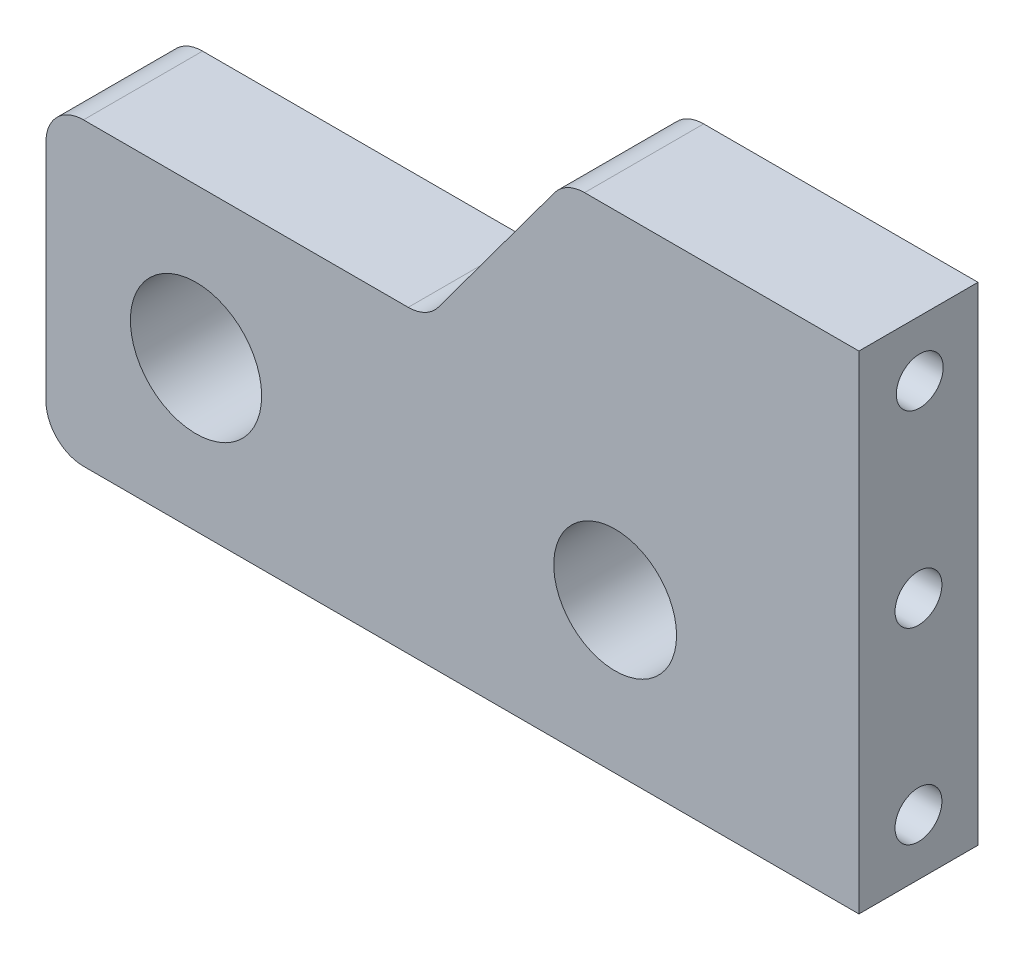
SolidWorks part; units mm, degrees
ref_plane "Front Plane" through (0, 0, 0) normal (0, 0, 1) x (1, 0, 0)
ref_plane "Top Plane" through (0, 0, 0) normal (0, 1, 0) x (1, 0, 0)
ref_plane "Right Plane" through (0, 0, 0) normal (1, 0, 0) x (0, 0, -1)
sketch "Sketch1" plane through (0, 0, 0) normal (0, 0, 1) x (1, 0, 0)
  line L0 (43.352, 8) -> (0, 8) construction
  line L1 (0, 0) -> (43.352, 0)
  line L2 (0, 0) -> (0, 16)
  line L3 (0, 16) -> (43.352, 16)
  line L4 (43.352, 0) -> (43.352, 16)
  circle A0 centre (8, 8) radius 3.5
  circle A1 centre (30.352, 8) radius 3.275
  dimension "D5" = 7
  dimension "D6" = 6.55
  dimension "D1" = 13
  dimension "D2" = 16
  dimension "D3" = 22.352
  dimension "D4" = 8
extrude "Boss-Extrude1" add sketch "Sketch1" along normal blind 6.35 contours L3 L4 L1 L2
extrude "Cut-Extrude1" cut sketch "Sketch1<6>" along normal blind 6.35 contours A0 L0 | L0 A0 | A1 region at (8, 6.5146, 0) region at (8, 9.4854, 0)
sketch "Sketch1<6>" plane through (0, 0, 0) normal (0, 0, 1) x (1, 0, 0) same geometry as "Sketch1"
fillet "Fillet1" radius 2 2 edges at (0, 16, 3.175) (0, 0, 3.175)
sketch "Sketch2" plane through (43.352, 0, 0) normal (1, 0, 0) x (0, 0, -1)
  line L0 (-6.35, 16) -> (0, 16) construction
  line L1 (-6.35, 0) -> (0, 0) construction
  line L4 (-6.35, 0) -> (-6.35, 16) construction
  circle A0 centre (-3.175, 13) radius 1.25
  circle A1 centre (-3.175, 3) radius 1.25
  dimension "D1" = 2.5
  dimension "D2" = 2.5
  dimension "D3" = 3
  dimension "D4" = 3
  dimension "D5" = 3.175
  dimension "D6" = 3.175
extrude "Cut-Extrude2" cut sketch "Sketch2" against normal blind 5
sketch "Sketch3" plane through (0, 0, 6.35) normal (0, 0, 1) x (1, 0, 0)
  line L0 (27.712, 26) -> (20.3263, 16)
  line L1 (43.352, 16) -> (27.712, 16)
  line L2 (43.352, 16) -> (43.352, 26)
  line L3 (43.352, 26) -> (27.712, 26)
  line L4 (27.712, 16) -> (27.712, 26)
  line L5 (2, 16) -> (43.352, 16) construction
  line M4 (43.352, 16) -> (2, 16)
  dimension "D1" = 10
extrude "Boss-Extrude2" add sketch "Sketch3" against normal blind 6.35 contours L4 L0 M4 | L4 L1 L2 L3 region at (25.2501, 19.3333, 6.35)
fillet "Fillet2" radius 2 2 edges at (20.3263, 16, 3.175) (27.712, 26, 3.175)
sketch "Sketch4" plane through (43.352, 0, 0) normal (1, 0, 0) x (0, 0, -1)
  line L0 (0, 26) -> (-6.35, 26) construction
  circle A0 centre (-3.1057, 23) radius 1.25
  dimension "D2" = 2.5
  dimension "D1" = 3
extrude "Cut-Extrude3" cut sketch "Sketch4" against normal blind 5
